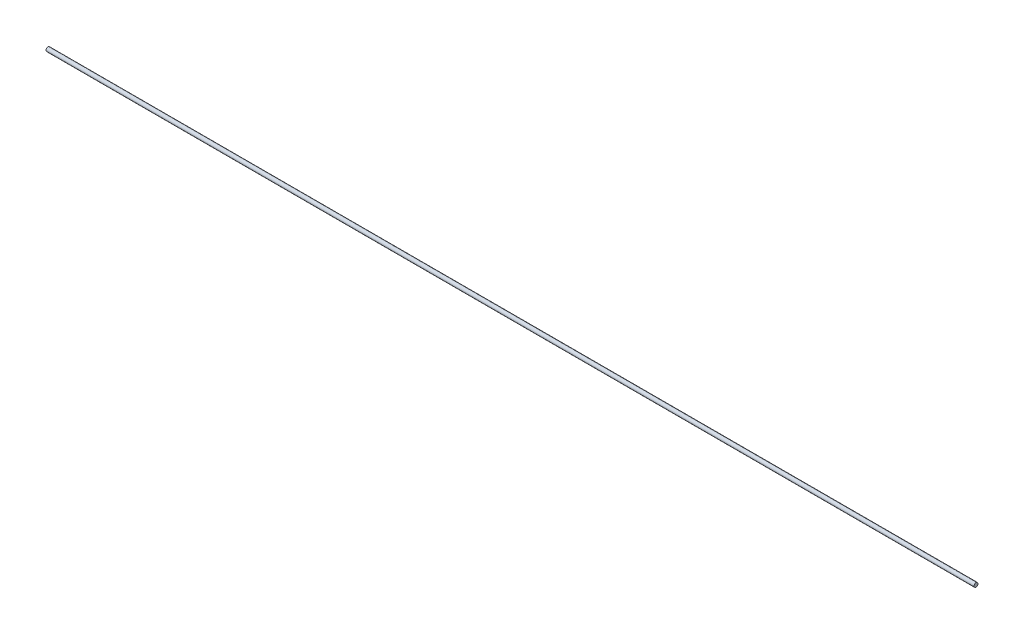
SolidWorks part; units mm, degrees
ref_plane "Front" through (0, 0, 0) normal (0, 0, 1) x (1, 0, 0)
ref_plane "Top" through (0, 0, 0) normal (0, 1, 0) x (1, 0, 0)
ref_plane "Right" through (0, 0, 0) normal (1, 0, 0) x (0, 0, -1)
sketch "Sketch1" plane through (0, 0, 0) normal (0, 0, 1) x (1, 0, 0)
  line L0 (0, 0) -> (34.3951, 0) construction
  line L1 (0, 0) -> (0, 3.175)
  line L2 (0, 3.175) -> (1469.4805, 3.175)
  line L3 (1469.4805, 3.175) -> (1469.4805, 0)
  line L4 (1469.4805, 0) -> (0, 0)
  line L5 (1469.4805, 3.25) -> (1469.4805, -3.25) construction
  point P5 (497.0851, 3.175)
  point P7 (1467.5069, 3.175)
  dimension "D1" = 6.35
revolve "Revolve1" add sketch "Sketch1" angle 360 about L0
